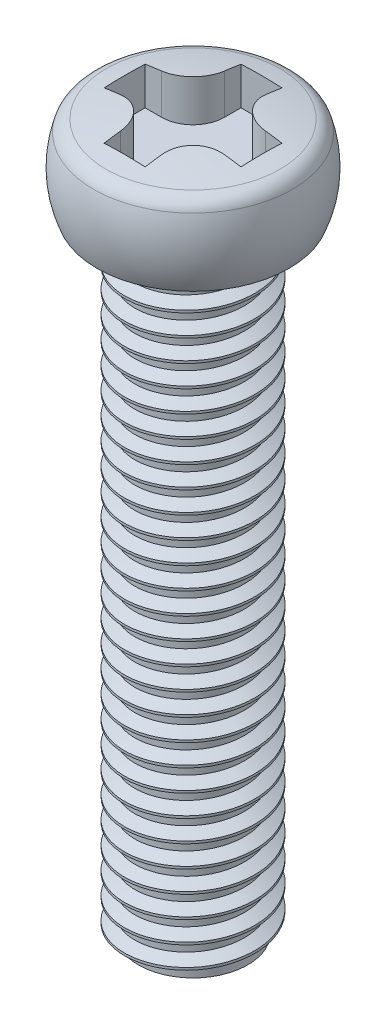
SolidWorks part; units mm, degrees
ref_plane "Front Plane" through (0, 0, 0) normal (0, 0, 1) x (1, 0, 0)
ref_plane "Top Plane" through (0, 0, 0) normal (0, 1, 0) x (1, 0, 0)
ref_plane "Right Plane" through (0, 0, 0) normal (1, 0, 0) x (0, 0, -1)
sketch "Sketch1" plane through (0, 0, 0) normal (0, 0, 1) x (1, 0, 0)
  line L0 (0, 1.65) -> (0, 1.45)
  line L1 (0, 0) -> (1.7562, 0)
  line L2 (0, 0) -> (0, 1.45)
  line L3 (0, 1.45) -> (1.7562, 1.45)
  line L4 (1.7562, 0) -> (1.7562, 1.45)
  line L5 (0, 1.65) -> (1.7562, 1.65) construction
  arc A0 (1.7562, 1.45) -> (0, 1.65) centre (0, -6.1609) ccw
  arc A1 (1.7562, 1.45) -> (1.7562, 0) centre (0, 0.725) cw
  point P9 (1.9, 0.725)
  dimension "D1" = 1.65
  dimension "D3" = 1.45
  dimension "D4" = 1.9
revolve "Revolve1" add sketch "Sketch1" angle 360 about L0
ref_plane "Plane1" through (0, 1.65, 0) normal (0, 1, 0) x (1, 0, 0)
sketch "Sketch2" plane through (0, 1.65, 0) normal (0, 1, 0) x (1, 0, 0)
  line L1 (0.375, -1.25) -> (-0.375, -1.25)
  line L2 (0.375, -1.25) -> (0.375, 1.25)
  line L3 (0.375, 1.25) -> (-0.375, 1.25)
  line L4 (-0.375, -1.25) -> (-0.375, 1.25)
  line L5 (0.375, -1.25) -> (-0.375, 1.25) construction
  line L6 (0.375, 1.25) -> (-0.375, -1.25) construction
  line L7 (1.25, -0.375) -> (-1.25, -0.375)
  line L8 (1.25, -0.375) -> (1.25, 0.375)
  line L9 (1.25, 0.375) -> (-1.25, 0.375)
  line L10 (-1.25, -0.375) -> (-1.25, 0.375)
  line L11 (1.25, -0.375) -> (-1.25, 0.375) construction
  line L12 (1.25, 0.375) -> (-1.25, -0.375) construction
  arc A0 (-0.375, 0.95) -> (-0.95, 0.375) centre (-0.95, 0.95) cw
  arc A1 (-0.95, -0.375) -> (-0.375, -0.95) centre (-0.95, -0.95) cw
  arc A2 (0.375, -0.95) -> (0.95, -0.375) centre (0.95, -0.95) cw
  arc A3 (0.95, 0.375) -> (0.375, 0.95) centre (0.95, 0.95) cw
  point P0 (0, 0)
  point P6 (0, 0)
  dimension "D3" = 0.3
  dimension "D1" = 2.5
  dimension "D2" = 0.75
extrude "Cut-Extrude1" cut sketch "Sketch2" against normal blind 0.8 contours L9 L2 L3 L4 | L4 A0 L9 | L10 L7 L4 L9 | L2 L9 L4 L7 | L2 L7 L4 L1 | L8 L9 L2 L7 | L9 A3 L2 | L2 A2 L7 | L7 A1 L4
sketch "Sketch3" plane through (0, 0, 0) normal (0, -1, 0) x (1, 0, 0)
  circle A0 centre (0, 0) radius 1
  dimension "D1" = 2
extrude "Boss-Extrude1" add sketch "Sketch3" along normal blind 11.4
thread "Thread1" pitch 0.35 start angle 0, offset 0, length 11.4, pitch 0.4, diameter 2
ref_plane "Plane2" through (1, 0, 0) normal (0, 0, 1) x (1, 0, 0)
sketch "Thread Profile1" plane through (1, 0, 0) normal (0, 0, 1) x (1, 0, 0)
  line L0 (0, 0) -> (0, 0.35) construction
  line L1 (0, 0) -> (0.1894, 0.1094)
  line L2 (0.1894, 0.1094) -> (0.1894, 0.1531)
  line L3 (0.1894, 0.1531) -> (0, 0.2625)
  line L4 (0.1894, 0.1312) -> (0, 0.1312) construction
  line L11 (0, 0) -> (0, 0.2625)
  point P2 (0, 0)
  dimension "Pitch" = 0.35
  dimension "Profile_Angle" = 60
  dimension "Profile_Land" = 0.0437
  dimension "Profile_Height" = 0.1894
fillet "Fillet1" radius 0.3 1 edges at (0, 1.45, 1.7562)
